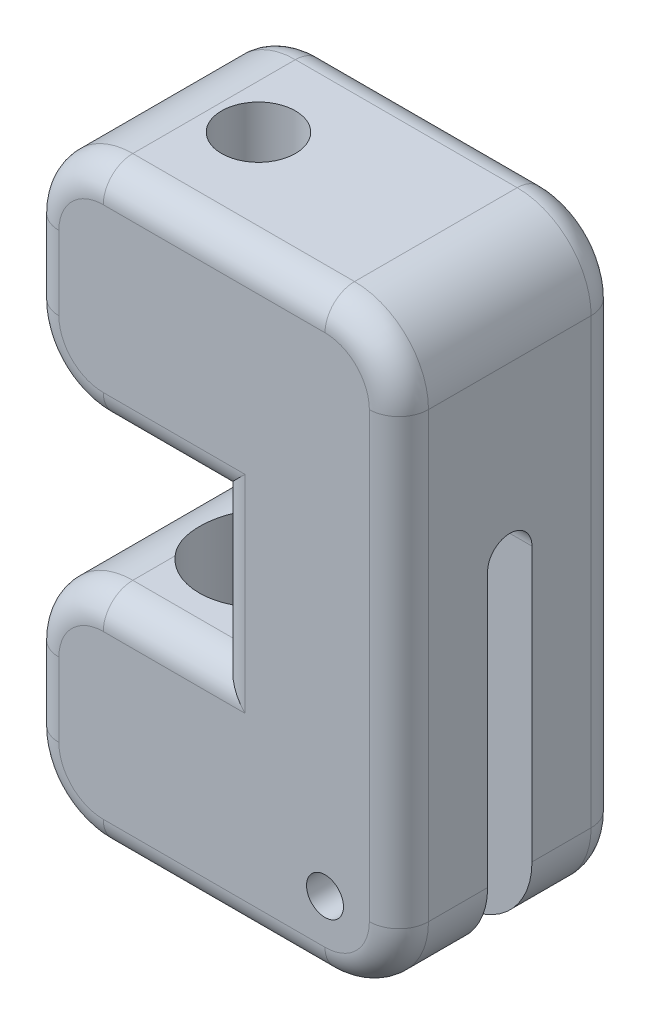
SolidWorks part; units mm, degrees
material "ABS"
ref_plane "Ebene vorne" through (0, 0, 0) normal (0, 0, 1) x (1, 0, 0)
ref_plane "Ebene oben" through (0, 0, 0) normal (0, 1, 0) x (1, 0, 0)
ref_plane "Ebene rechts" through (0, 0, 0) normal (1, 0, 0) x (0, 0, -1)
sketch "Skizze1" plane through (0, 0, 0) normal (0, 1, 0) x (1, 0, 0)
  line L0 (17, 0) -> (-8, 0) construction
  line L1 (-8, 7.5) -> (17, 7.5)
  line L2 (-8, 7.5) -> (-8, -7.5)
  line L3 (-8, -7.5) -> (17, -7.5)
  line L4 (17, 7.5) -> (17, -7.5)
  circle A0 centre (0, 0) radius 4
  dimension "D1" = 8
  dimension "D2" = 25
  dimension "D3" = 8
  dimension "D4" = 15
extrude "Aufsatz-Linear austragen1" add sketch "Skizze1" along normal blind 40
sketch "Skizze2" plane through (0, 40, 0) normal (0, 1, 0) x (1, 0, 0)
  line L0 (0, 0) -> (23.7529, 0) construction
  line L1 (0, 1.5) -> (23.7529, 1.5)
  line L2 (0, -1.5) -> (23.7529, -1.5)
  arc A0 (0, 1.5) -> (0, -1.5) centre (0, 0) ccw
  arc A1 (23.7529, -1.5) -> (23.7529, 1.5) centre (23.7529, 0) ccw
  point P3 (11.8764, 0)
  dimension "D1" = 3
extrude "Schnitt-Linear austragen1" cut sketch "Skizze2" against normal blind 71 from offset 15 offset against normal yes
hole_wizard "M3 Gewindebohrung1" positions "Skizze4" profile "Skizze3" tap size "M3" standard "DIN" end condition through all
sketch "Skizze4" plane through (0, 0, 7.5) normal (0, 0, 1) x (1, 0, 0)
  line L2 (17, 40) -> (17, 0) construction
  line L3 (-8, 0) -> (17, 0) construction
  point P1 (12, 5)
  dimension "D1" = 5
  dimension "D2" = 5
cosmetic thread "Bohrungsgewinde1" parameters "D2"=3
sketch "Skizze3" plane through (12, 5, 7.5) normal (1, 0, 0) x (0, -1, 0)
  line L0 (0, 0) -> (0, 15)
  line L1 (0, 15) -> (1.25, 15)
  line L2 (1.25, 15) -> (1.25, 0)
  line L5 (1.25, 0) -> (0, 0)
  line L11 (0, -6.35) -> (0, 107.95) construction
  dimension "Bohrerdurchmesser" = 2.5
  dimension "Bohrungstiefe" = 15
fillet "Verrundung2" radius 2 2 edges at (3.7081, 12.5, 1.5) (3.7081, 12.5, -1.5)
sketch "Skizze5" plane through (0, 0, 0) normal (0, 0, 1) x (1, 0, 0)
  line L0 (-8, 40) -> (17, 40) construction
  line L1 (-12.5107, 25) -> (4.5888, 25)
  line L2 (-12.5107, 25) -> (-12.5107, 15)
  line L3 (-12.5107, 15) -> (4.5888, 15)
  line L4 (4.5888, 25) -> (4.5888, 15)
  line L5 (-8, 0) -> (17, 0) construction
  dimension "D1" = 15
  dimension "D2" = 15
extrude "Schnitt-Linear austragen2" cut sketch "Skizze5" against normal mid plane 26
sketch "Skizze6" plane through (0, 40, 0) normal (0, 1, 0) x (1, 0, 0)
  circle A0 centre (0, 0) radius 2.5
  circle A1 centre (0, 0) radius 4 construction
  circle A2 centre (0, 0) radius 4
  dimension "D1" = 5
extrude "Aufsatz-Linear austragen2" add sketch "Skizze6" against normal up to surface (15 mm away) up to face at (4.6101, 25, 0)
fillet "Verrundung5" radius 5 7 edges at (-8, 0, 0) (-8, 15, 0) (-8, 25, 0) (-8, 40, 0) (17, 40, 0) (17, 0, -4.5) (17, 0, 4.5)
fillet "Verrundung6" radius 2 28 edges at (0.7944, 15, -7.5) (-6.5355, 13.5355, -7.5) (-8, 7.5, -7.5) (-6.5355, 1.4645, -7.5) (4.5, 0, -7.5) (15.5355, 1.4645, -7.5) (17, 20, -7.5) (15.5355, 38.5355, -7.5) (0.7944, 25, -7.5) (-6.5355, 26.4645, -7.5) (-8, 32.5, -7.5) (-6.5355, 38.5355, -7.5) (0.7944, 25, 7.5) (-6.5355, 26.4645, 7.5) (-8, 32.5, 7.5) (-6.5355, 38.5355, 7.5) (0.7944, 15, 7.5) (-6.5355, 13.5355, 7.5) (-8, 7.5, 7.5) (-6.5355, 1.4645, 7.5) (4.5, 0, 7.5) (15.5355, 1.4645, 7.5) (17, 20, 7.5) (15.5355, 38.5355, 7.5) (4.5888, 20, -7.5) (4.5, 40, -7.5) (4.5888, 20, 7.5) (4.5, 40, 7.5)
fillet "Verrundung7" radius 1.5 4 edges at (4.7307, 25, 1.5051) (4.7307, 25, -1.5051) (10.9367, 25, 1.5) (10.9367, 25, -1.5)
